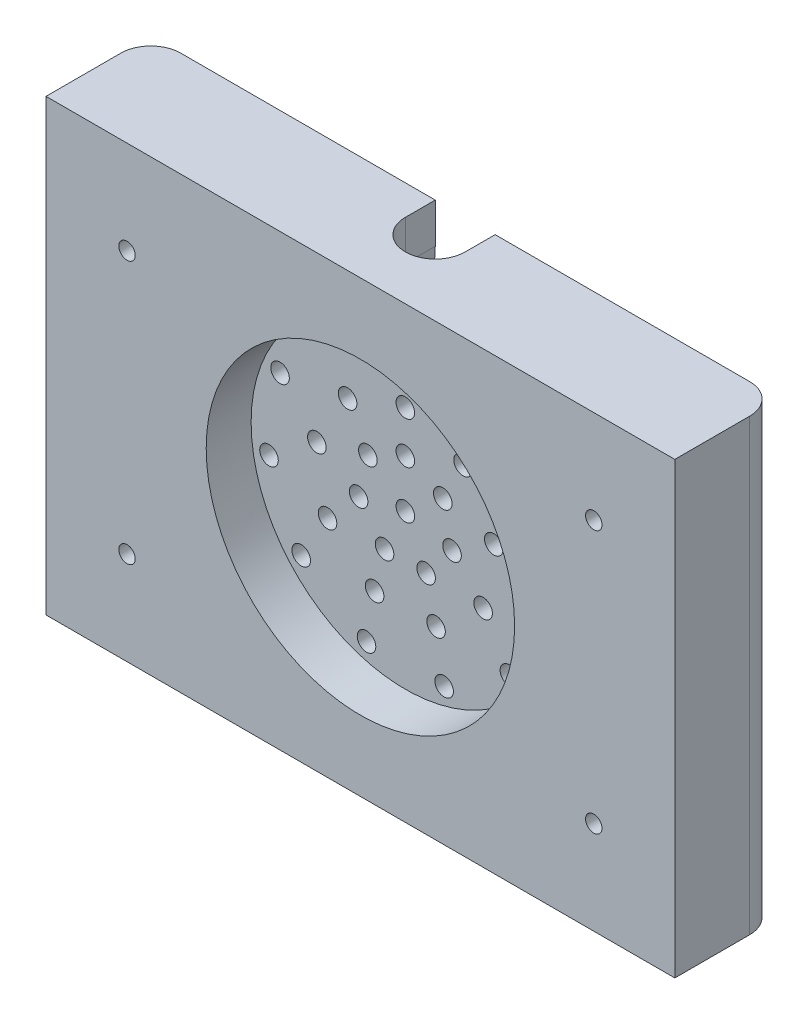
SolidWorks part; units mm, degrees
ref_plane "Front Plane" through (0, 0, 0) normal (0, 0, 1) x (1, 0, 0)
ref_plane "Top Plane" through (0, 0, 0) normal (0, 1, 0) x (1, 0, 0)
ref_plane "Right Plane" through (0, 0, 0) normal (1, 0, 0) x (0, 0, -1)
sketch "Sketch1" plane through (0, 0, 0) normal (0, 0, 1) x (1, 0, 0)
  circle A0 centre (0, 0) radius 56
extrude "Boss-Extrude1" add sketch "Sketch1" along normal blind 25
sketch "Sketch2" plane through (0, 0, 25) normal (0, 0, 1) x (1, 0, 0)
  line L1 (105, -75) -> (-105, -75)
  line L2 (105, -75) -> (105, 75)
  line L3 (105, 75) -> (-105, 75)
  line L4 (-105, -75) -> (-105, 75)
  line L5 (105, -75) -> (-105, 75) construction
  line L6 (105, 75) -> (-105, -75) construction
  circle A0 centre (0, 0) radius 51.5
  point P0 (0, 0)
  dimension "D1" = 210
  dimension "D2" = 150
extrude "Boss-Extrude2" add sketch "Sketch2" against normal blind 35
sketch "Sketch3" plane through (0, 0, 0) normal (0, 0, -1) x (-1, 0, 0)
  line L0 (0, 0) -> (0, 16) construction
  line L1 (0, 0) -> (12.5093, 9.9758) construction
  line L2 (0, 0) -> (0, 46) construction
  line L3 (0, 0) -> (24.8695, 38.6977) construction
  circle A0 centre (0, 46) radius 3.1
  circle A1 centre (0, 30) radius 3.1
  circle A2 centre (0, 16) radius 3.1
  circle A3 centre (12.5093, 9.9758) radius 3.1
  circle A4 centre (15.5988, -3.5603) radius 3.1
  circle A5 centre (6.9421, -14.4155) radius 3.1
  circle A6 centre (-6.9421, -14.4155) radius 3.1
  circle A7 centre (-15.5988, -3.5603) radius 3.1
  circle A8 centre (-12.5093, 9.9758) radius 3.1
  circle A9 centre (19.2836, 22.9813) radius 3.1
  circle A10 centre (29.5442, 5.2094) radius 3.1
  circle A11 centre (25.9808, -15) radius 3.1
  circle A12 centre (10.2606, -28.1908) radius 3.1
  circle A13 centre (-10.2606, -28.1908) radius 3.1
  circle A14 centre (-25.9808, -15) radius 3.1
  circle A15 centre (-29.5442, 5.2094) radius 3.1
  circle A16 centre (-19.2836, 22.9813) radius 3.1
  circle A17 centre (24.8695, 38.6977) radius 3.1
  circle A18 centre (41.8431, 19.1091) radius 3.1
  circle A19 centre (45.5318, -6.5465) radius 3.1
  circle A20 centre (34.7645, -30.1236) radius 3.1
  circle A21 centre (12.9597, -44.1367) radius 3.1
  circle A22 centre (-12.9597, -44.1367) radius 3.1
  circle A23 centre (-34.7645, -30.1236) radius 3.1
  circle A24 centre (-45.5318, -6.5465) radius 3.1
  circle A25 centre (-41.8431, 19.1091) radius 3.1
  circle A26 centre (-24.8695, 38.6977) radius 3.1
  circle A27 centre (0, 0) radius 3.1
  point P41 (0, 0)
  dimension "D1" = 14
  dimension "D2" = 16
  dimension "D3" = 16
  dimension "D5" = 51.429
  dimension "D8" = 32.727
  dimension "D4" = 7
  dimension "D6" = 9
  dimension "D7" = 11
extrude "Cut-Extrude1" cut sketch "Sketch3" against normal through all
sketch "Sketch7" plane through (0, 0, 25) normal (0, 0, 1) x (1, 0, 0)
  circle A0 centre (0, 0) radius 51.5
extrude "Cut-Extrude2" cut sketch "Sketch7" against normal blind 15
hole_wizard "CBORE for M5 Hex Bolt Grade C1" positions "3DSketch4" profile "Sketch12" counterbore size "M5" standard "AS" end condition through all
sketch3d "3DSketch4"
  line L0 (0, 0, 0) -> (77.9423, 43.8748, -10) construction
  line L1 (0, 0, 0) -> (118.1192, 0, 0) construction
  line L2 (77.9423, -43.8748, -10) -> (0, 0, 0) construction
  line L3 (0, 0, 0) -> (-77.9423, 43.8748, -10) construction
  line L5 (0, 0, 0) -> (-111.443, 0, 0) construction
  line L6 (0, 0, 0) -> (-77.9423, -43.8748, -10) construction
  point P0 (77.9423, 43.8748, -10)
  point P8 (77.9423, -43.8748, -10)
  point P10 (-77.9423, 43.8748, -10)
  point P12 (-77.9423, -43.8748, -10)
  dimension "D1" = 90
  dimension "D2" = 30
  dimension "D3" = 90
  dimension "D4" = 30
  dimension "D5" = 90
  dimension "D6" = 30
  dimension "D7" = 90
  dimension "D8" = 30
sketch "Sketch12" plane through (77.9423, 43.8748, -10) normal (1, 0, 0) x (0, 1, 0)
  line L0 (0, 0) -> (0, 35)
  line L1 (0, 35) -> (2.75, 35)
  line L3 (2.75, 35) -> (2.75, 3.5)
  line L4 (6.119, 3.5) -> (2.75, 3.5)
  line L5 (6.119, 3.5) -> (6.119, 0.0241)
  line L6 (6.119, 0.0241) -> (6.144, 0)
  line L7 (6.144, 0) -> (0, 0)
  line L8 (-6.119, 0.0241) -> (-6.144, 0) construction
  line L11 (0, -6.35) -> (0, 107.95) construction
  dimension "Thru Hole Dia." = 5.5
  dimension "Thru Hole Depth" = 35
  dimension "C'Bore Dia." = 12.238
  dimension "C'Bore Depth" = 3.5
  dimension "Near C'Sink Dia." = 12.288
  dimension "Near C'Sink Angle" = 92
sketch "Sketch17" plane through (0, 0, -10) normal (0, 0, -1) x (-1, 0, 0)
  line L0 (0, 0) -> (0, 65.672) construction
  line L2 (10, 45.672) -> (-10, 45.672)
  line L3 (10, 45.672) -> (10, 85.672)
  line L4 (10, 85.672) -> (-10, 85.672)
  line L5 (-10, 45.672) -> (-10, 85.672)
  line L6 (10, 45.672) -> (-10, 85.672) construction
  line L7 (10, 85.672) -> (-10, 45.672) construction
  point P3 (0, 65.672)
  dimension "D1" = 20
  dimension "D2" = 40
  dimension "D3" = 65.672
extrude "Cut-Extrude4" cut sketch "Sketch17" against normal up to surface (10 mm away) up to face at (-3.1, 46, 0)
sketch "Sketch18" plane through (0, 75, 0) normal (0, 1, 0) x (1, 0, 0)
  circle A0 centre (0, 0) radius 10
extrude "Cut-Extrude5" cut sketch "Sketch18" against normal blind 22.5
fillet "Fillet6" radius 10 2 edges at (105, 0, -10) (-105, 0, -10)
fillet "Fillet7" radius 15 2 edges at (10, 50.5198, -5) (-10, 50.5198, -5) conic rho 0.6
